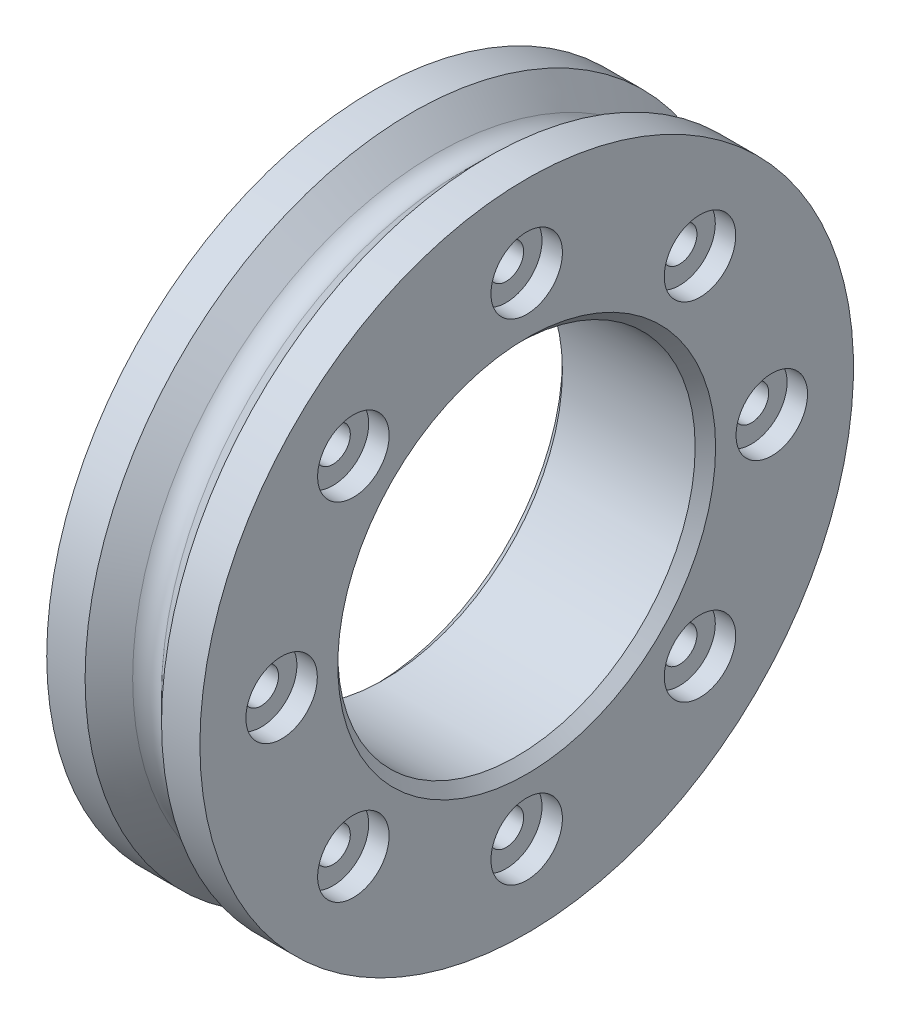
SolidWorks part; units mm, degrees
ref_plane "Front Plane" through (0, 0, 0) normal (0, 0, 1) x (1, 0, 0)
ref_plane "Top Plane" through (0, 0, 0) normal (0, 1, 0) x (1, 0, 0)
ref_plane "Right Plane" through (0, 0, 0) normal (1, 0, 0) x (0, 0, -1)
sketch "Sketch1" plane through (0, 0, 0) normal (0, 0, 1) x (1, 0, 0)
  line L0 (-33.7322, 0) -> (0, 0) construction
  line L1 (0, 0) -> (0, 40.25) construction
  line L2 (0, 36.7426) -> (4.2426, 32.5)
  line L3 (7.5, 47.5) -> (-7.5, 47.5) construction
  line L4 (7.5, 47.5) -> (7.5, 33) construction
  line L5 (7.5, 33) -> (-7.5, 33) construction
  line L6 (-7.5, 47.5) -> (-7.5, 33) construction
  line L7 (7.5, 47.5) -> (-7.5, 33) construction
  line L8 (7.5, 33) -> (-7.5, 47.5) construction
  line L9 (7.5, 32) -> (-7.5, 32)
  line L10 (7.5, 32) -> (7.5, 17.5)
  line L11 (7.5, 17.5) -> (-7.5, 17.5)
  line L12 (-7.5, 32) -> (-7.5, 17.5)
  line L13 (7.5, 32) -> (-7.5, 17.5) construction
  line L14 (7.5, 17.5) -> (-7.5, 32) construction
  line L15 (0, 36.7426) -> (-4.2426, 32.5)
  line L16 (4.2426, 32.5) -> (0, 28.2574)
  line L17 (-4.2426, 32.5) -> (0, 28.2574)
  line L18 (0, 36.7426) -> (0, 28.2574) construction
  line L19 (4.2426, 32.5) -> (-4.2426, 32.5) construction
  point P9 (0, 24.75)
  point P15 (0, 32.5)
  dimension "D1" = 17.5
  dimension "D2" = 47.5
  dimension "D3" = 15
  dimension "D4" = 14.5
  dimension "D5" = 0.5
  dimension "D6" = 6
revolve "Revolve1" add sketch "Sketch1" angle 360 about L0 region at (0, 24.3368, 0)
ref_axis "Axis2" through (7.5, 0, 0) along (-1, 0, 0)
chamfer "Chamfer1" distance 1 angle 45 2 edges at (7.5, 0, 17.5) (-7.5, 0, 17.5)
fillet "Fillet1" radius 2 1 edges at (0, 0, 28.2574)
sketch "Sketch2" plane through (7.5, 0, 0) normal (1, 0, 0) x (0, 0, -1)
  line L0 (0, 24) -> (0, 0) construction
  circle A0 centre (0, 0) radius 24 construction
  dimension "D1" = 48
hole_wizard "CBORE for M3 Hex Head Cap Screw1" positions "3DSketch2" profile "Sketch3" counterbore size "M3" standard "ISO" end condition through all
sketch3d "3DSketch2"
  point P0 (7.5, 24, 0)
sketch "Sketch3" plane through (7.5, 24, 0) normal (0, 1, 0) x (0, 0, -1)
  line L0 (0, 0) -> (0, 15)
  line L1 (0, 15) -> (1.7, 15)
  line L3 (1.7, 15) -> (1.7, 2)
  line L4 (1.7, 2) -> (3.5, 2)
  line L5 (3.5, 2) -> (3.5, 0)
  line L7 (3.5, 0) -> (0, 0)
  line L11 (0, -6.35) -> (0, 107.95) construction
  dimension "Thru Hole Dia." = 3.4
  dimension "Thru Hole Depth" = 15
  dimension "C'Bore Dia." = 7
  dimension "C'Bore Depth" = 2
pattern_circular "CirPattern1" count 8 over 360 about axis through (7.5, 0, 0) along (-1, 0, 0) of "CBORE for M3 Hex Head Cap Screw1"
